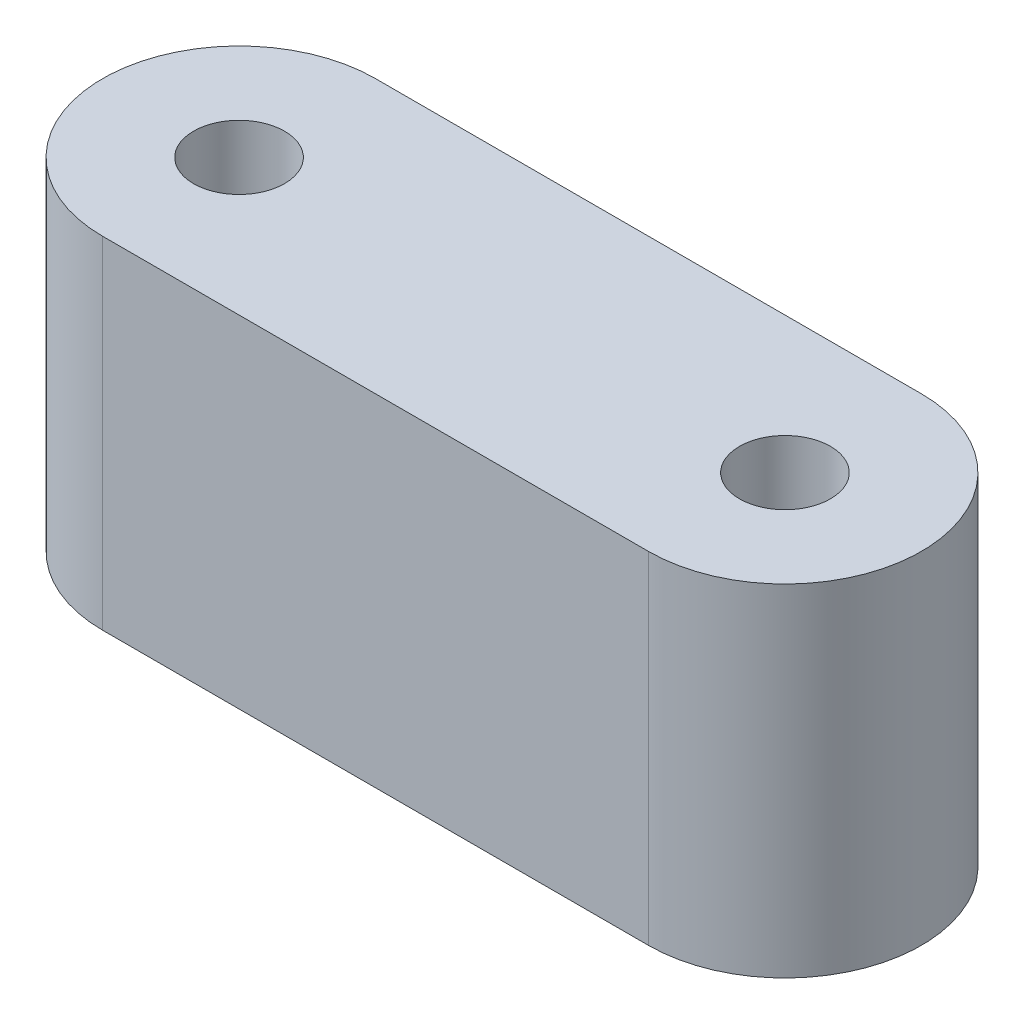
SolidWorks part; units mm, degrees
material "ABS"
ref_plane "Front Plane" through (0, 0, 0) normal (0, 0, 1) x (1, 0, 0)
ref_plane "Top Plane" through (0, 0, 0) normal (0, 1, 0) x (1, 0, 0)
ref_plane "Right Plane" through (0, 0, 0) normal (1, 0, 0) x (0, 0, -1)
sketch "Sketch1" plane through (0, 0, 0) normal (0, 1, 0) x (1, 0, 0)
  line L0 (-12, 0) -> (12, 0) construction
  line L1 (-12, 0) -> (12, 0) construction
  line L2 (-12, 6) -> (12, 6)
  line L3 (-12, -6) -> (12, -6)
  circle A0 centre (-12, 0) radius 2
  circle A1 centre (12, 0) radius 2
  arc A2 (-12, 6) -> (-12, -6) centre (-12, 0) ccw
  arc A3 (12, -6) -> (12, 6) centre (12, 0) ccw
  point P6 (0, 0)
  dimension "D2" = 4
  dimension "D3" = 4
  dimension "D1" = 24
extrude "Boss-Extrude1" add sketch "Sketch1" along normal blind 15
sketch "Sketch2" plane through (0, 0, 0) normal (0, -1, 0) x (1, 0, 0)
  line L1 (-13.8331, 3.175) -> (-15.6662, 0)
  line L2 (-15.6662, 0) -> (-13.8331, -3.175)
  line L3 (-13.8331, -3.175) -> (-10.1669, -3.175)
  line L4 (-10.1669, -3.175) -> (-8.3338, 0)
  line L5 (-8.3338, 0) -> (-10.1669, 3.175)
  line L6 (-10.1669, 3.175) -> (-13.8331, 3.175)
  circle A0 centre (-12, 0) radius 3.175 construction
  dimension "D1" = 6.35
extrude "Cut-Extrude1" cut sketch "Sketch2" against normal blind 6
mirror "Mirror1" about plane through (0, 0, 0) normal (1, 0, 0) of "Cut-Extrude1"
